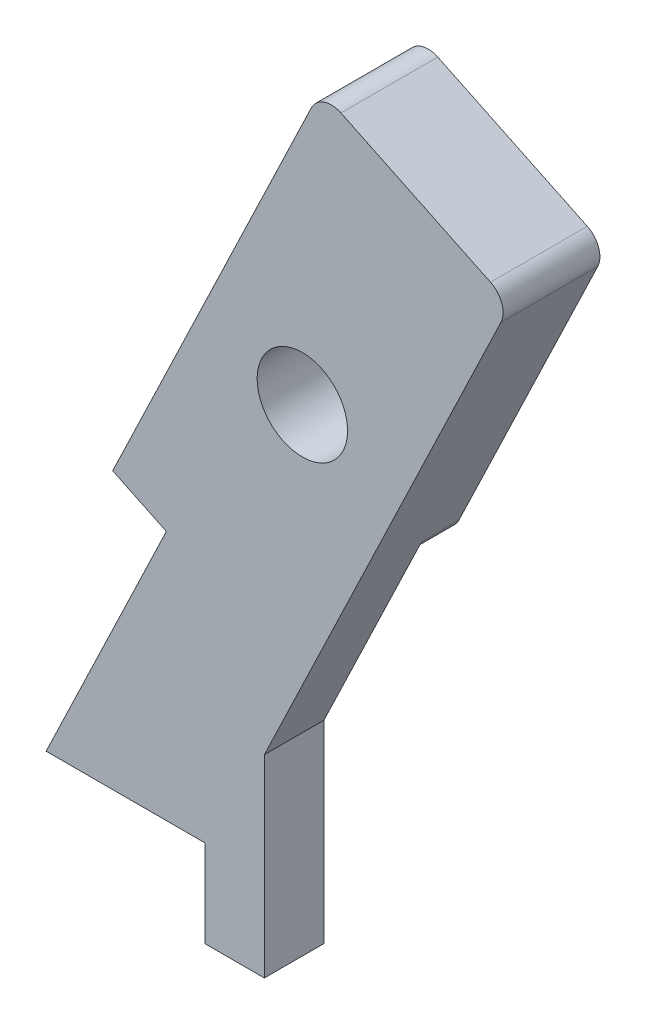
SolidWorks part; units mm, degrees
ref_plane "Front Plane" through (0, 0, 0) normal (0, 0, 1) x (1, 0, 0)
ref_plane "Top Plane" through (0, 0, 0) normal (0, 1, 0) x (1, 0, 0)
ref_plane "Right Plane" through (0, 0, 0) normal (1, 0, 0) x (0, 0, -1)
sketch "Sketch1" plane through (0, 0, 0) normal (0, 0, 1) x (1, 0, 0)
  line L1 (-126.5001, -28.5917) -> (-101.1001, -28.5917)
  line L6 (-126.5001, -28.5917) -> (-107.2589, 11.478)
  line L7 (-107.2589, 11.478) -> (-115.8452, 15.6011)
  line L8 (-101.1001, -42.5617) -> (-101.1001, -28.5917)
  line L9 (-101.1001, -42.5617) -> (-91.5751, -42.5617)
  line L11 (-91.5751, -42.5617) -> (-91.5751, -11.6044)
  line L12 (-53.7243, 67.2195) -> (-75.9342, 20.9677) construction
  line L13 (-79.3179, 83.4541) -> (-55.3906, 71.9644) construction
  line L14 (54.8646, 243.2901) -> (-49.5876, 25.769) construction
  line L15 (-106.2726, 35.536) -> (-84.0628, 81.7878) construction
  line L16 (-53.7243, 67.2195) -> (-91.5751, -11.6044)
  line L17 (-79.3179, 83.4541) -> (-55.3906, 71.9644)
  line L18 (-115.8452, 15.6011) -> (-84.0628, 81.7878)
  arc A0 (-53.7243, 67.2195) -> (-55.3906, 71.9644) centre (-56.9299, 68.7588) ccw construction
  arc A1 (-79.3179, 83.4541) -> (-84.0628, 81.7878) centre (-80.8572, 80.2486) ccw construction
  arc A2 (-53.7243, 67.2195) -> (-55.3906, 71.9644) centre (-56.9299, 68.7588) ccw
  arc A3 (-79.3179, 83.4541) -> (-84.0628, 81.7878) centre (-80.8572, 80.2486) ccw
  circle A4 centre (-85.496, 39.9293) radius 7.239 construction
  circle A5 centre (-85.496, 39.9293) radius 7.239
  point P4 (-30.7884, -27.3042)
  point P9 (0, 0)
  point P16 (0, 0)
  point P19 (0, 0)
  point P20 (-6.5182, -51.2341)
  dimension "D3" = 9.525
  dimension "D4" = 9.525
  dimension "D6" = 64.35
  dimension "D7" = 44.45
  dimension "D8" = 13.97
  dimension "D9" = 25.4
extrude "Boss-Extrude1" add sketch "Sketch1" along normal blind 9.525
sketch "Sketch2" plane through (0, 0, 0) normal (0, 0, -1) x (-1, 0, 0)
  line L10 (106.2726, 35.536) -> (84.0628, 81.7878)
  line L11 (79.3179, 83.4541) -> (55.3906, 71.9644)
  line L12 (53.7243, 67.2195) -> (75.9342, 20.9677)
  line L13 (80.679, 19.3014) -> (104.6064, 30.7911)
  line L14 (106.2726, 35.536) -> (84.0628, 81.7878)
  line L15 (79.3179, 83.4541) -> (55.3906, 71.9644)
  line L16 (53.7243, 67.2195) -> (75.9342, 20.9677)
  line L17 (80.679, 19.3014) -> (104.6064, 30.7911)
  circle A0 centre (85.496, 39.9293) radius 7.239 construction
  circle A1 centre (85.496, 39.9293) radius 7.239
  arc A4 (104.6064, 30.7911) -> (106.2726, 35.536) centre (103.0671, 33.9967) ccw
  arc A5 (84.0628, 81.7878) -> (79.3179, 83.4541) centre (80.8572, 80.2486) ccw
  arc A6 (55.3906, 71.9644) -> (53.7243, 67.2195) centre (56.9299, 68.7588) ccw
  arc A7 (75.9342, 20.9677) -> (80.679, 19.3014) centre (79.1397, 22.507) ccw
  arc A8 (104.6064, 30.7911) -> (106.2726, 35.536) centre (103.0671, 33.9967) ccw
  arc A9 (84.0628, 81.7878) -> (79.3179, 83.4541) centre (80.8572, 80.2486) ccw
  arc A10 (55.3906, 71.9644) -> (53.7243, 67.2195) centre (56.9299, 68.7588) ccw
  arc A11 (75.9342, 20.9677) -> (80.679, 19.3014) centre (79.1397, 22.507) ccw
  dimension "D1" = 0
extrude "Boss-Extrude2" add sketch "Sketch2" along normal blind 5.969
